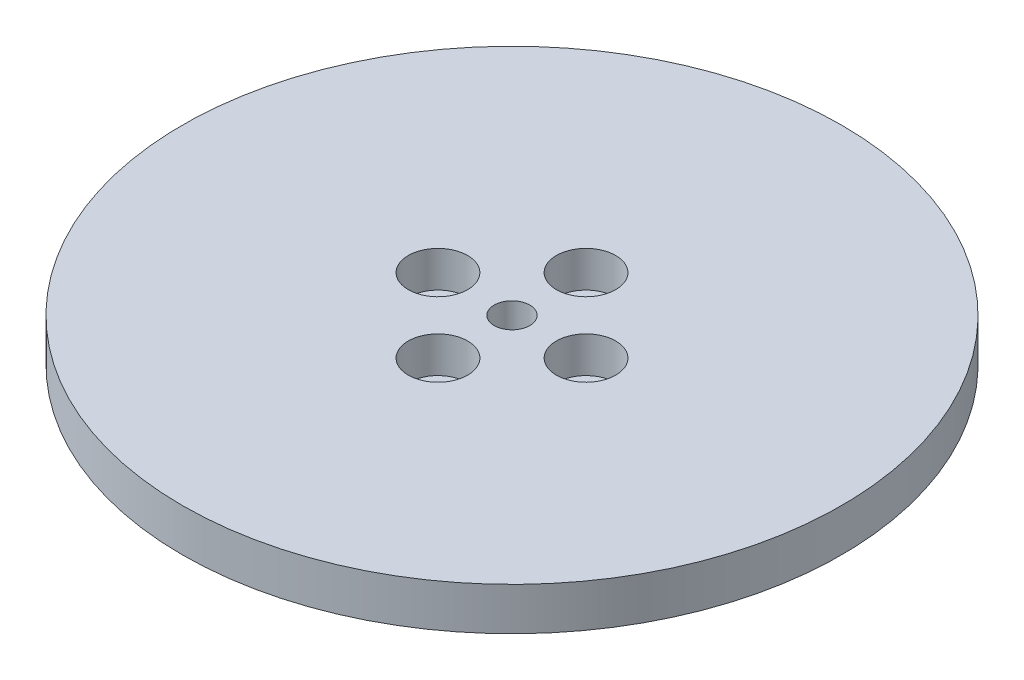
SolidWorks part; units mm, degrees
ref_plane "Front Plane" through (0, 0, 0) normal (0, 0, 1) x (1, 0, 0)
ref_plane "Top Plane" through (0, 0, 0) normal (0, 1, 0) x (1, 0, 0)
ref_plane "Right Plane" through (0, 0, 0) normal (1, 0, 0) x (0, 0, -1)
sketch "Sketch1" plane through (0, 0, 0) normal (0, 1, 0) x (1, 0, 0)
  circle A0 centre (0, 0) radius 92.5
  dimension "FLANGE_OD" = 185
extrude "Boss-Extrude1" add sketch "Sketch1" along normal blind 12
sketch "Sketch2" plane through (0, 0, 0) normal (0, 1, 0) x (1, 0, 0)
  circle A0 centre (0, 0) radius 5
  dimension "BORE_D" = 10
extrude "Cut-Extrude1" cut sketch "Sketch2" along normal through all
sketch "Sketch3" plane through (0, 12, 0) normal (0, 1, 0) x (1, 0, 0)
  circle A0 centre (0, 0) radius 20.7801 construction
  circle A1 centre (-20.7801, 0) radius 8.3245
  dimension "BOLT_D" = 16.649
  dimension "BOLT_PCD" = 41.5602
extrude "Cut-Extrude2" cut sketch "Sketch3" against normal blind 10.1461
pattern_circular "CirPattern1" count 4 over 360 about axis through (0, 0, 0) along (0, 1, 0) of "Cut-Extrude2"
